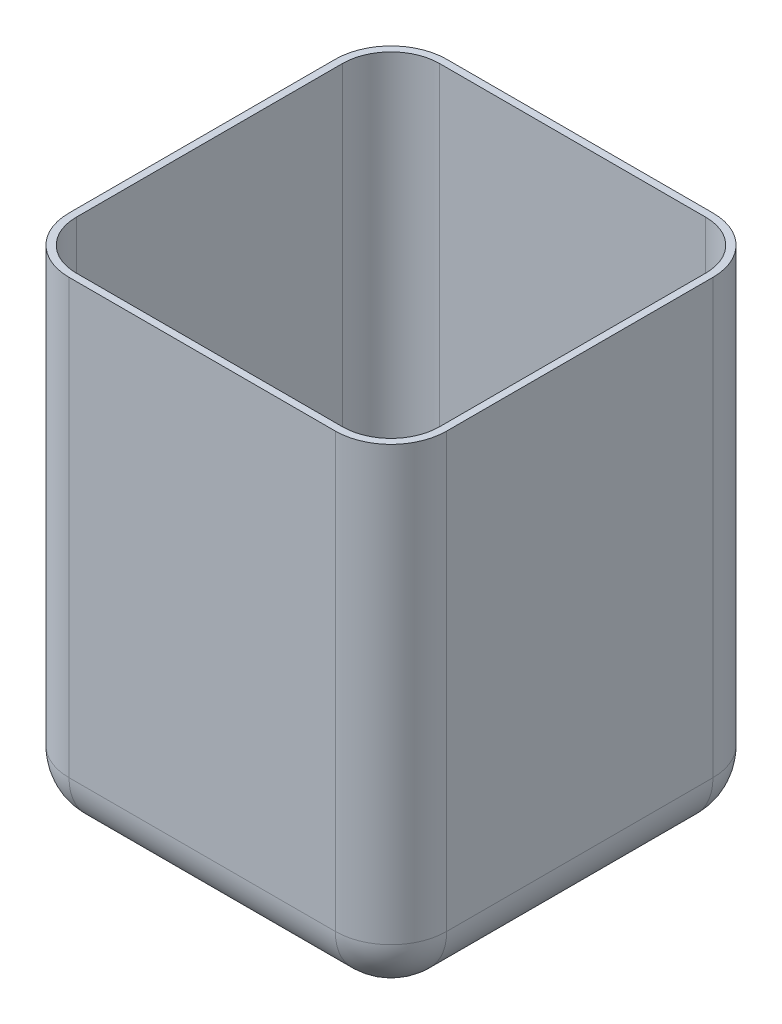
SolidWorks part; units mm, degrees
ref_plane "Front Plane" through (0, 0, 0) normal (0, 0, 1) x (1, 0, 0)
ref_plane "Top Plane" through (0, 0, 0) normal (0, 1, 0) x (1, 0, 0)
ref_plane "Right Plane" through (0, 0, 0) normal (1, 0, 0) x (0, 0, -1)
sketch "Sketch1" plane through (0, 0, 0) normal (0, 1, 0) x (1, 0, 0)
  line L1 (-69.2308, 55.3902) -> (86.7692, 55.3902)
  line L2 (-69.2308, 55.3902) -> (-69.2308, -100.6098)
  line L3 (-69.2308, -100.6098) -> (86.7692, -100.6098)
  line L4 (86.7692, 55.3902) -> (86.7692, -100.6098)
  dimension "D1" = 156
  dimension "D2" = 156
extrude "Boss-Extrude1" add sketch "Sketch1" along normal blind 202
fillet "Fillet1" radius 23 8 edges at (8.7692, 0, 100.6098) (86.7692, 0, 22.6098) (8.7692, 0, -55.3902) (-69.2308, 0, 22.6098) (86.7692, 101, -55.3902) (-69.2308, 101, -55.3902) (86.7692, 101, 100.6098) (-69.2308, 101, 100.6098)
shell "Shell1" thickness 3 removed face at (8.7692, 202, 22.6098)
